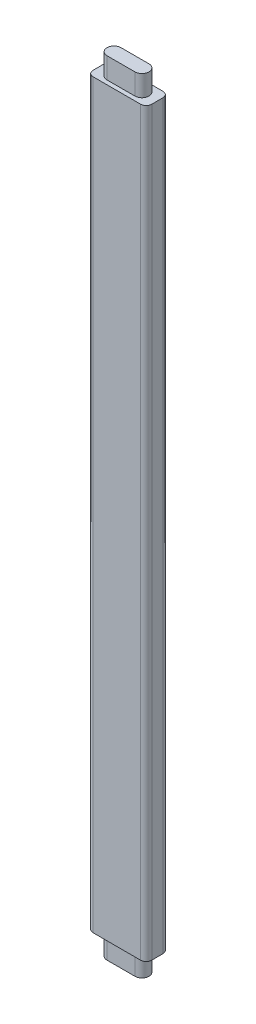
SolidWorks part; units mm, degrees
ref_plane "Front" through (0, 0, 0) normal (0, 0, 1) x (1, 0, 0)
ref_plane "Top" through (0, 0, 0) normal (0, 1, 0) x (1, 0, 0)
ref_plane "Right" through (0, 0, 0) normal (1, 0, 0) x (0, 0, -1)
sketch "Esquisse1" plane through (0, 0, 0) normal (0, 1, 0) x (1, 0, 0)
  line L1 (0, 0) -> (42, 0)
  line L2 (0, 0) -> (0, 16)
  line L3 (0, 16) -> (42, 16)
  line L4 (42, 0) -> (42, 16)
  dimension "D1" = 42
  dimension "D2" = 16
extrude "Boss.-Extru.1" add sketch "Esquisse1" along normal blind 530
sketch "Esquisse2" plane through (0, 530, 0) normal (0, 1, 0) x (1, 0, 0)
  line L0 (42, 8) -> (0, 8) construction
  line L1 (42, 0) -> (42, 16) construction
  line L2 (0, 16) -> (0, 0) construction
  line L3 (11, 8) -> (31, 8) construction
  line L4 (11, 13) -> (31, 13)
  line L5 (11, 3) -> (31, 3)
  arc A0 (11, 13) -> (11, 3) centre (11, 8) ccw
  arc A1 (31, 3) -> (31, 13) centre (31, 8) ccw
  point P8 (21, 8)
  dimension "D1" = 10
  dimension "D2" = 20
extrude "Boss.-Extru.2" add sketch "Esquisse2" along normal blind 15
extrude "Boss.-Extru.3" add sketch "Esquisse2<2>" against normal blind 15 from vertex starting at point (42, 0, 0)
sketch "Esquisse2<2>" plane through (0, 530, 0) normal (0, 1, 0) x (1, 0, 0) same geometry as "Esquisse2"
fillet "Congé1" radius 4 4 edges at (42, 265, 0) (42, 265, -16) (0, 265, -16) (0, 265, 0)
